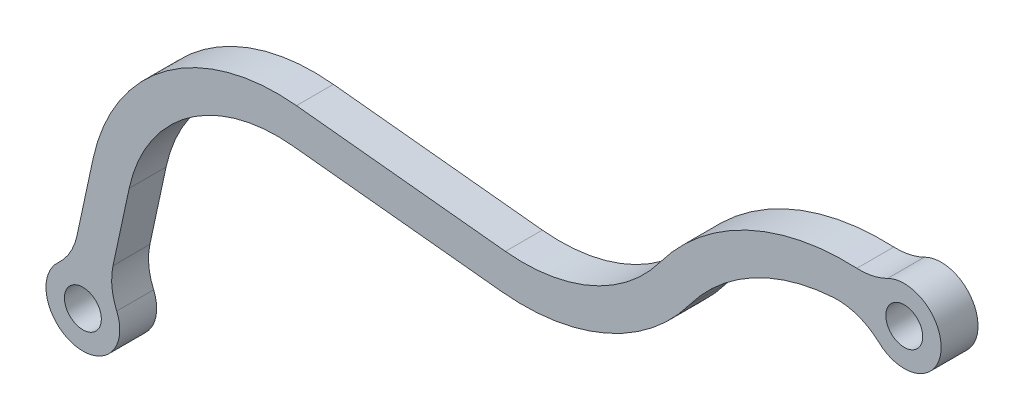
SolidWorks part; units mm, degrees
ref_plane "Спереди" through (0, 0, 0) normal (0, 0, 1) x (1, 0, 0)
ref_plane "Сверху" through (0, 0, 0) normal (0, 1, 0) x (1, 0, 0)
ref_plane "Справа" through (0, 0, 0) normal (1, 0, 0) x (0, 0, -1)
other "Configuration Table"
sketch "Sketch1" plane through (0, 0, 0) normal (0, 0, 1) x (1, 0, 0)
  line L0 (34.8557, 20.2376) -> (17.8642, 22.0056)
  line L1 (30.9283, 23.6624) -> (21.4794, 24.6456) construction
  line L2 (2.9521, 11.192) -> (0.6537, 0.5285)
  circle A0 centre (0.6537, 0.5285) radius 3 construction
  circle A1 centre (0.6537, 0.5285) radius 3
  arc A2 (70.3356, 33.4669) -> (64.5425, 31.9047) centre (67.439, 32.6858) ccw construction
  arc A3 (70.3356, 33.4669) -> (64.5425, 31.9047) centre (67.439, 32.6858) ccw construction
  circle A4 centre (67.439, 32.6858) radius 3
  arc A5 (67.439, 32.6858) -> (48.7874, 26.3611) centre (62.6863, 16.0371) ccw
  arc A6 (48.7874, 26.3611) -> (34.8557, 20.2376) centre (36.4467, 35.5277) cw
  arc A7 (17.8642, 22.0056) -> (2.9521, 11.192) centre (16.4366, 8.2856) ccw
  arc A8 (27.3821, 20.9871) -> (24.3988, 21.2975) centre (25.8934, 21.1702) ccw construction
  arc A9 (27.3821, 20.9871) -> (24.3988, 21.2975) centre (25.8934, 21.1702) ccw
extrude "Extrude-Thin1" add sketch "Sketch1" along normal blind 3 thin contours A5 A6 L0 A7 L2 thin type mid plane wall 3
extrude "Boss-Extrude1" add sketch "Sketch1<3>" along normal through all contours A1 | A4 region at (2.9218, 2.3599, 0)
sketch "Sketch1<3>" plane through (0, 0, 0) normal (0, 0, 1) x (1, 0, 0) same geometry as "Sketch1"
fillet "Fillet1" radius 5 4 edges at (64.5935, 31.7354, 1.5) (65.1998, 34.6822, 1.5) (2.6674, 2.7522, 1.5) (-0.2652, 3.3843, 1.5)
hole_wizard "Ø3.0 mm Dowel Holes1" positions "Sketch2" profile "Sketch3" hole size "Ø3.0" standard "ISO" end condition through all
sketch "Sketch2" plane through (0, 0, 3) normal (0, 0, 1) x (1, 0, 0)
  arc A0 (65.3957, 30.4893) -> (66.0842, 35.3624) centre (67.439, 32.6858) ccw construction
  arc A1 (65.3957, 30.4893) -> (66.0842, 35.3624) centre (67.439, 32.6858) ccw
  point P0 (67.439, 32.6858)
  point P2 (0.6537, 0.5285)
sketch "Sketch3" plane through (67.439, 32.6858, 3) normal (1, 0, 0) x (0, -1, 0)
  line L0 (0, 0) -> (0, 3)
  line L1 (0, 3) -> (1.5, 3)
  line L2 (1.5, 3) -> (1.5, 0)
  line L5 (1.5, 0) -> (0, 0)
  line L11 (0, -6.35) -> (0, 107.95) construction
  dimension "Thru Hole Dia." = 3
  dimension "Thru Hole Depth" = 3
